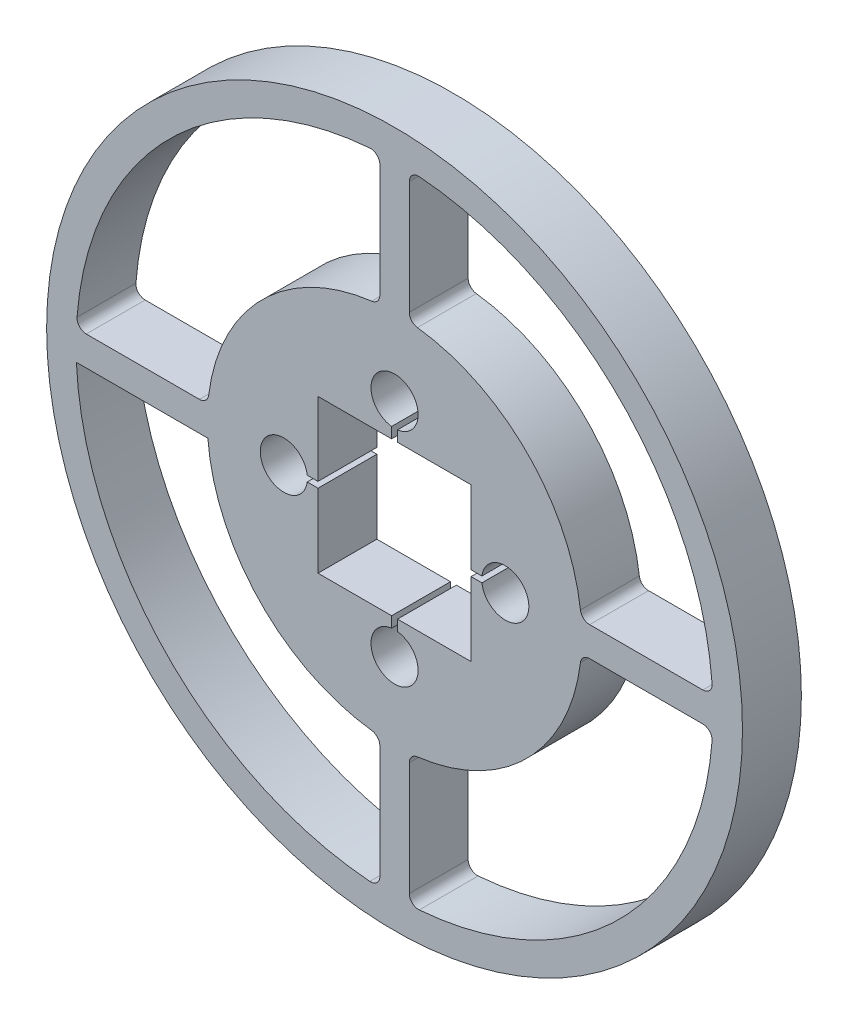
SolidWorks part; units mm, degrees
material "AISI 1020"
ref_plane "Front Plane" through (0, 0, 0) normal (0, 0, 1) x (1, 0, 0)
ref_plane "Top Plane" through (0, 0, 0) normal (0, 1, 0) x (1, 0, 0)
ref_plane "Right Plane" through (0, 0, 0) normal (1, 0, 0) x (0, 0, -1)
other "Center of Mass"
sketch "Sketch1" plane through (0, 0, 0) normal (0, 0, 1) x (1, 0, 0)
  line L0 (-11.938, 0) -> (0, 0) construction
  line L1 (-8.255, 8.255) -> (8.255, 8.255)
  line L2 (-8.255, 8.255) -> (-8.255, -8.255)
  line L3 (-8.255, -8.255) -> (8.255, -8.255)
  line L4 (8.255, 8.255) -> (8.255, -8.255)
  line L5 (0, 0) -> (0, 11.938) construction
  line L6 (11.938, 0) -> (0, 0) construction
  line L7 (0, 0) -> (0, -11.938) construction
  line L9 (-9.4179, 0.3175) -> (9.4179, 0.3175)
  line L10 (-9.4179, 0.3175) -> (-9.4179, -0.3175)
  line L11 (-9.4179, -0.3175) -> (9.4179, -0.3175)
  line L12 (9.4179, 0.3175) -> (9.4179, -0.3175)
  line L13 (-0.3175, 9.4179) -> (0.3175, 9.4179)
  line L14 (-0.3175, 9.4179) -> (-0.3175, -9.4179)
  line L15 (-0.3175, -9.4179) -> (0.3175, -9.4179)
  line L16 (0.3175, 9.4179) -> (0.3175, -9.4179)
  line L17 (-1.5875, 20.1305) -> (-1.5875, 34.3041)
  line L19 (1.5875, 20.1305) -> (1.5875, 34.3041)
  line L20 (20.1305, 1.5875) -> (34.3041, 1.5875)
  line L21 (20.1305, -1.5875) -> (34.3041, -1.5875)
  line L22 (1.5875, -20.1305) -> (1.5875, -34.3041)
  line L23 (-1.5875, -20.1305) -> (-1.5875, -34.3041)
  line L24 (-20.1305, -1.5875) -> (-34.3041, -1.5875)
  line L25 (-20.1305, 1.5875) -> (-34.3041, 1.5875)
  circle A1 centre (0, 11.938) radius 2.54
  circle A2 centre (0, -11.938) radius 2.54
  circle A3 centre (11.938, 0) radius 2.54
  circle A4 centre (-11.938, 0) radius 2.54
  circle A68 centre (0, 0) radius 37.5158
  arc A73 (-1.5875, 34.3041) -> (-34.3041, 1.5875) centre (0, 0) ccw
  arc A75 (-1.5875, 20.1305) -> (-20.1305, 1.5875) centre (0, 0) ccw
  arc A76 (20.1305, 1.5875) -> (1.5875, 20.1305) centre (0, 0) ccw
  arc A77 (34.3041, 1.5875) -> (1.5875, 34.3041) centre (0, 0) ccw
  arc A78 (1.5875, -20.1305) -> (20.1305, -1.5875) centre (0, 0) ccw
  arc A79 (1.5875, -34.3041) -> (34.3041, -1.5875) centre (0, 0) ccw
  arc A80 (-20.1305, -1.5875) -> (-1.5875, -20.1305) centre (0, 0) ccw
  arc A81 (-34.3041, -1.5875) -> (-1.5875, -34.3041) centre (0, 0) ccw
  point P7 (8.255, 0)
  point P8 (0, 8.255)
  point P46 (0, 0)
  point P54 (0, 0)
  point P70 (0, 0)
  point P77 (0, 0)
  point P104 (0, 0)
  dimension "D2" = 18.8358
  dimension "D4" = 5.08
  dimension "D6" = 3.175
  dimension "D7" = 40.386
  dimension "D5" = 75.0316
  dimension "D1" = 16.51
  dimension "D3" = 11.938
  dimension "D8" = 3.175
extrude "Boss-Extrude1" add sketch "Sketch1" along normal blind 6.35 contours A4 L9 L2 L1 L14 A1 L16 L4 A3 L11 L3 A2 region at (-36.4547, 0, 0)
fillet "Fillet2" radius 1 14 edges at (1.5875, -34.3041, 3.175) (34.3041, -1.5875, 3.175) (20.1305, -1.5875, 3.175) (1.5875, -20.1305, 3.175) (-1.5875, -20.1305, 3.175) (-1.5875, -34.3041, 3.175) (-20.1305, 1.5875, 3.175) (-1.5875, 20.1305, 3.175) (1.5875, 34.3041, 3.175) (-1.5875, 34.3041, 3.175) (1.5875, 20.1305, 3.175) (20.1305, 1.5875, 3.175) (34.3041, 1.5875, 3.175) (-34.3041, 1.5875, 3.175)
